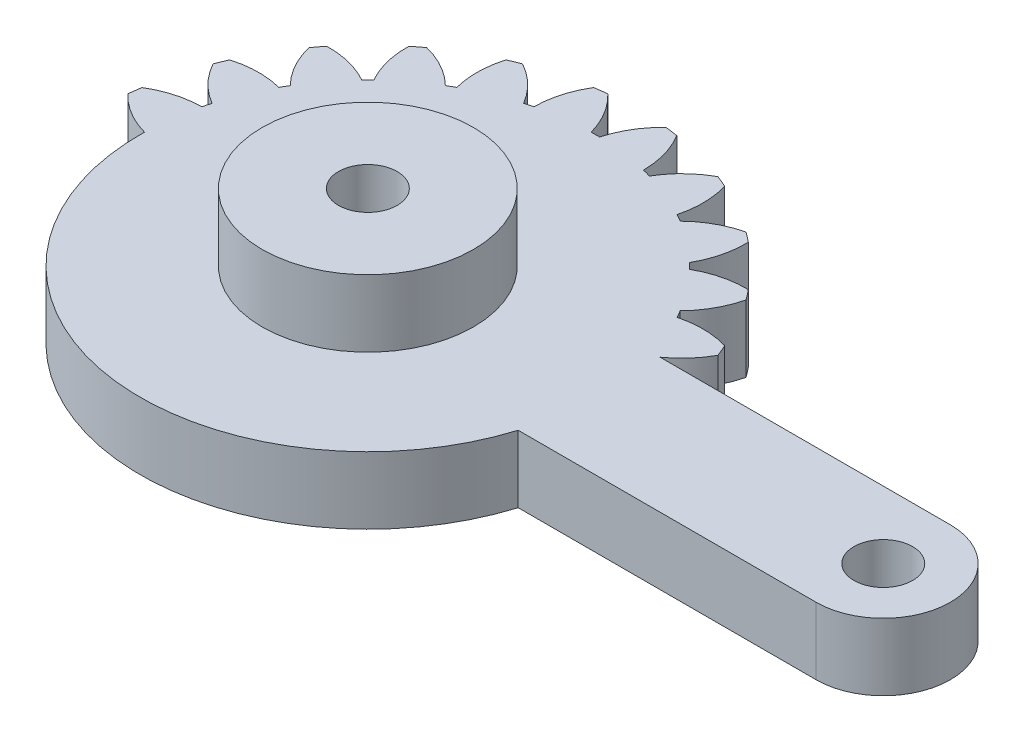
SolidWorks part; units mm, degrees
ref_plane "Ön Düzlem" through (0, 0, 0) normal (0, 0, 1) x (1, 0, 0)
ref_plane "Üst Düzlem" through (0, 0, 0) normal (0, 1, 0) x (1, 0, 0)
ref_plane "Sağ Düzlem" through (0, 0, 0) normal (1, 0, 0) x (0, 0, -1)
sketch "Çizim1" plane through (0, 0, 0) normal (0, 1, 0) x (1, 0, 0)
  line L0 (-55, 0) -> (55, 0) construction
  line L3 (0, 15.9439) -> (0, 10.0716)
  line L4 (0, -55) -> (0, 55) construction
  arc A0 (1.7298, 16.037) -> (-1.7298, 16.037) centre (0, 0) ccw
  arc A1 (0.25, 13.5627) -> (-0.25, 13.5627) centre (0, 0) ccw
  circle A2 centre (0, 0) radius 1.75
  circle A3 centre (-5, 0) radius 1.3
  circle A4 centre (5, 0) radius 1.3
  arc A5 (-0.25, 13.5627) -> (-1.7298, 16.037) centre (-5.4561, 12.1287) ccw
  arc A6 (0.25, 13.5627) -> (1.7298, 16.037) centre (5.4561, 12.1287) cw
  dimension "D1" = 32.26
  dimension "D2" = 27.13
  dimension "D3" = 3.5
  dimension "D4" = 2.6
  dimension "D5" = 2.6
  dimension "D8" = 10.8
  dimension "D9" = 0.5
  dimension "D6" = 10
  dimension "D7" = 5
sketch "Çizim2" plane through (0, 0, 0) normal (0, 1, 0) x (1, 0, 0)
  circle A0 centre (0, 0) radius 1.75
  circle A1 centre (5, 0) radius 1.3
  circle A2 centre (-5, 0) radius 1.2999
  circle A3 centre (0, 0) radius 16.13
  dimension "D1" = 32.26
extrude "Yükseklik-Ekstrüzyon1" add sketch "Çizim2" along normal blind 4
extrude "Kes-Ekstrüzyon2" cut sketch "Çizim1" along normal blind 4 contours A1 A6 A0 L3 | A5 A1 L3 A0 region at (0.7848, 0, -14.9225)
pattern_circular "Dairesel Kaplama2" count 24 over 360 about axis through (0, 4, 0) along (0, 1, 0) of "Kes-Ekstrüzyon2"
sketch "Çizim4" plane through (0, 0, 0) normal (0, 1, 0) x (1, 0, 0)
  line L2 (11.3826, 4) -> (22.8585, 4)
  line L3 (11.3826, -4) -> (22.3917, -4)
  line L4 (22.8585, 4) -> (30.7226, 4)
  line L5 (22.3917, -4) -> (30.7226, -4)
  arc A0 (11.3826, -4) -> (11.3826, 4) centre (0, 0) ccw
  circle A1 centre (30.7226, 0) radius 1.75
  arc A2 (30.7226, -4) -> (30.7226, 4) centre (30.7226, 0) ccw
  dimension "D3" = 3.5
  dimension "D1" = 8
  dimension "D2" = 19.34
extrude "Yükseklik-Ekstrüzyon2" add sketch "Çizim4" along normal blind 4
sketch "Çizim5" plane through (0, 0, 0) normal (0, 1, 0) x (1, 0, 0)
  line L0 (-13.565, 0) -> (-18.5294, 0)
  line L1 (-55, 0) -> (55, 0) construction
  line L2 (-18.5294, 0) -> (-18.5294, -18.2112)
  line L3 (-18.5294, -18.2112) -> (15.6616, -18.5769)
  line L4 (15.6616, -18.5769) -> (15.6616, -4)
  line L5 (13.4206, -4) -> (30.7226, -4) construction
  line L6 (15.6616, -4) -> (12.9618, -4)
  arc A0 (-13.565, 0) -> (12.9618, -4) centre (0, 0) ccw
extrude "Kes-Ekstrüzyon3" cut sketch "Çizim5" along normal blind 4
sketch "Çizim7" plane through (0, 0, 0) normal (0, 1, 0) x (1, 0, 0)
  circle A0 centre (0, 0) radius 6.2999
  circle A1 centre (0, 0) radius 1.75
extrude "Yükseklik-Ekstrüzyon3" add sketch "Çizim7" along normal blind 8
